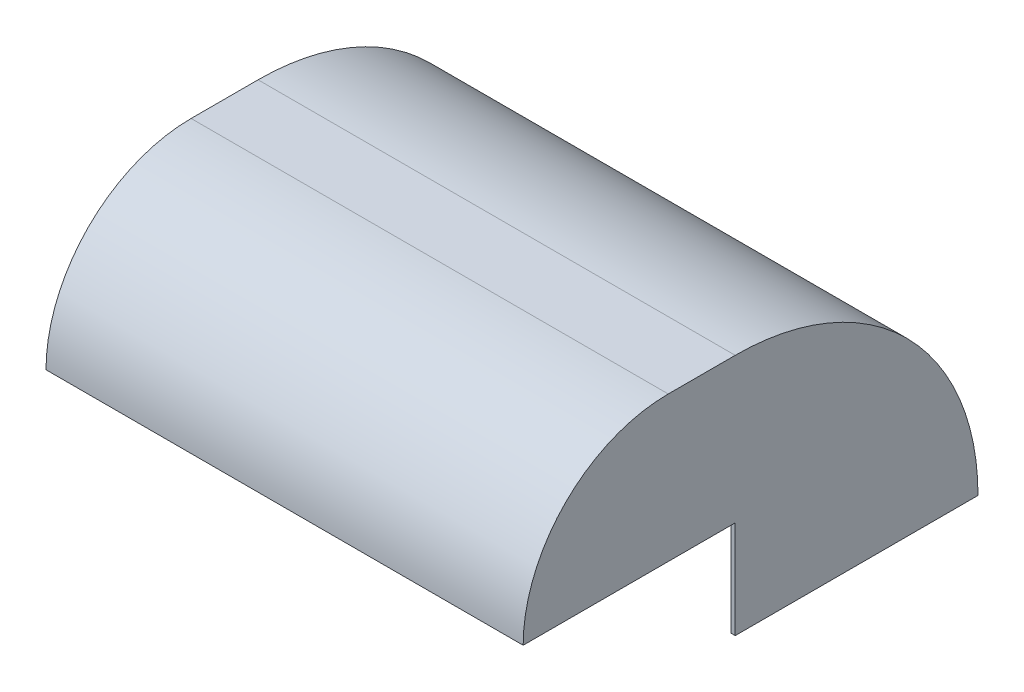
SolidWorks part; units mm, degrees
ref_plane "Front Plane" through (0, 0, 0) normal (0, 0, 1) x (1, 0, 0)
ref_plane "Top Plane" through (0, 0, 0) normal (0, 1, 0) x (1, 0, 0)
ref_plane "Right Plane" through (0, 0, 0) normal (1, 0, 0) x (0, 0, -1)
sketch "Sketch1" plane through (0, 0, 0) normal (0, 1, 0) x (1, 0, 0)
  line L0 (-16.4646, 32.3013) -> (-16.4646, -18.4987)
  line L1 (-13.2896, 29.1263) -> (13.6979, 29.1263)
  line L2 (-13.2896, 29.1263) -> (-13.2896, -15.3237)
  line L3 (-13.2896, -15.3237) -> (13.6979, -15.3237)
  line L4 (13.6979, 29.1263) -> (13.6979, -15.3237)
  line L5 (-16.4646, -18.4987) -> (16.8729, -18.4987)
  line L6 (16.8729, 32.3013) -> (16.8729, -18.4987)
  line L7 (-16.4646, 32.3013) -> (16.8729, 32.3013)
  line L8 (-16.4646, 32.3013) -> (-132.3521, 32.3013)
  line L9 (-132.3521, 32.3013) -> (-132.3521, -27.5039)
  line L10 (-248.2396, 32.3013) -> (-281.5771, 32.3013)
  line L11 (-281.5771, 32.3013) -> (-281.5771, -18.4987)
  line L12 (-248.2396, -18.4987) -> (-281.5771, -18.4987)
  line L13 (-248.2396, 32.3013) -> (-248.2396, -18.4987)
  line L14 (-251.4146, 29.1263) -> (-251.4146, -15.3237)
  line L15 (-251.4146, -15.3237) -> (-278.4021, -15.3237)
  line L16 (-278.4021, 29.1263) -> (-278.4021, -15.3237)
  line L17 (-251.4146, 29.1263) -> (-278.4021, 29.1263)
  line L18 (-13.2896, -15.3237) -> (-251.4146, -15.3237) construction
  dimension "D1" = 3.175
  dimension "D2" = 13.6979
  dimension "D3" = 13.2896
  dimension "D4" = 132.3521
  dimension "D5" = 29.1263
  dimension "D6" = 15.3237
  dimension "D7" = 27.5039
extrude "Boss-Extrude1" add sketch "Sketch1" along normal blind 25.4 contours L4 L1 L2 L3 | L0 L5 L6 L7 region at (0.2042, 0, -6.9013)
fillet "Fillet2" radius 2.54 4 edges at (13.6979, 12.7, 15.3237) (13.6979, 12.7, -29.1263) (-13.2896, 12.7, 15.3237) (-13.2896, 12.7, -29.1263)
sketch "Sketch2" plane through (0, 25.4, 0) normal (0, 1, 0) x (1, 0, 0)
  line L1 (16.8729, -18.4987) -> (-16.4646, -18.4987)
  line L2 (16.8729, -18.4987) -> (16.8729, 32.3013)
  line L3 (16.8729, 32.3013) -> (-16.4646, 32.3013)
  line L4 (-16.4646, -18.4987) -> (-16.4646, 32.3013)
extrude "Boss-Extrude2" add sketch "Sketch2" along normal blind 1.5875
extrude "Boss-Extrude3" add sketch "Sketch1<5>" along normal blind 26.9875 separate body contours L10 L11 L12 L13
sketch "Sketch1<5>" plane through (0, 0, 0) normal (0, 1, 0) x (1, 0, 0) same geometry as "Sketch1"
extrude "Cut-Extrude1" cut sketch "Sketch1<6>" along normal blind 25.4 contours L15 L16 L17 L14
sketch "Sketch1<6>" plane through (0, 0, 0) normal (0, 1, 0) x (1, 0, 0) same geometry as "Sketch1"
fillet "Fillet4" radius 2.54 4 edges at (-251.4146, 12.7, -29.1263) (-278.4021, 12.7, -29.1263) (-251.4146, 12.7, 15.3237) (-278.4021, 12.7, 15.3237)
ref_plane "Plane2" through (16.8729, 0, 0) normal (1, 0, 0) x (0, 0, -1)
sketch "Sketch3" plane through (16.8729, 0, 0) normal (1, 0, 0) x (0, 0, -1)
  line L0 (32.3013, 26.9875) -> (32.3013, -157.1625)
sketch "Sketch4" plane through (16.8729, 0, 0) normal (1, 0, 0) x (0, 0, -1)
  line L0 (32.3013, -157.1625) -> (216.4513, -157.1625)
  line L2 (32.3013, -157.1625) -> (32.3013, 26.9875)
  circle A0 centre (32.3013, -157.1625) radius 184.15
  circle A1 centre (32.3013, -157.1625) radius 180.975
sketch "Sketch5" plane through (0, 0, 0) normal (0, 1, 0) x (1, 0, 0)
  line L0 (16.8729, -18.4987) -> (-281.5771, -18.4987)
extrude "Boss-Extrude4" add sketch "Sketch4" against normal blind 330.2 and the other way blind 31.75 contours A1 L0 A0 L2 region at (16.8729, -27.3524, -162.1115)
ref_plane "Plane3" through (0, 0, -32.3013) normal (0, 0, 1) x (1, 0, 0)
sketch "Sketch6" plane through (0, 0, -32.3013) normal (0, 0, 1) x (1, 0, 0)
  line L1 (-248.2396, 26.9875) -> (-16.4646, 26.9875)
  line L2 (-248.2396, 26.9875) -> (-248.2396, 23.8125)
  line L3 (-248.2396, 23.8125) -> (-16.4646, 23.8125)
  line L4 (-16.4646, 26.9875) -> (-16.4646, 23.8125)
extrude "Boss-Extrude5" add sketch "Sketch6" along normal through all contours L2 L1 L4 L3
sketch "Sketch7" plane through (16.8729, 0, 0) normal (1, 0, 0) x (0, 0, -1)
  line L0 (-18.4987, 26.9875) -> (-18.4987, -83.0707)
  line L1 (-18.4987, -83.0707) -> (-128.5569, -83.0707)
  circle A0 centre (-18.4987, -83.0707) radius 110.0582
  circle A1 centre (-18.4987, -83.0707) radius 106.8324
extrude "Boss-Extrude6" add sketch "Sketch7" against normal blind 330.2 and the other way blind 31.75 contours A1 L0 A0 L1 region at (16.8729, 25.3746, 20.0551)
ref_plane "Plane4" through (48.6229, 0, 0) normal (1, 0, 0) x (0, 0, -1)
sketch "Sketch9" plane through (48.6229, 0, 0) normal (1, 0, 0) x (0, 0, -1)
  line L0 (32.3013, -157.1625) -> (32.3013, 26.9875)
  line L1 (32.3013, -157.1625) -> (216.4513, -157.1625)
  circle A0 centre (32.3013, -157.1625) radius 184.15
  circle A1 centre (32.3013, -157.1625) radius 180.975
extrude "Boss-Extrude7" add sketch "Sketch9" against normal blind 3.175 contours L1 A1 L0 region at (48.6229, -80.3543, -109.1095)
sketch "Sketch10" plane through (16.8729, 0, 0) normal (1, 0, 0) x (0, 0, -1)
  line L1 (32.3013, 26.9875) -> (-18.4987, 26.9875)
  line L2 (32.3013, 26.9875) -> (32.3013, 23.7617)
  line L3 (32.3013, 23.7617) -> (-18.4987, 23.7617)
  line L4 (-18.4987, 26.9875) -> (-18.4987, 23.7617)
extrude "Boss-Extrude8" add sketch "Sketch10" along normal blind 31.75
sketch "Sketch11" plane through (0, 0, -32.3013) normal (0, 0, 1) x (1, 0, 0)
  line L1 (45.4479, 23.7617) -> (48.6229, 23.7617)
  line L2 (45.4479, 23.7617) -> (45.4479, -157.1625)
  line L3 (45.4479, -157.1625) -> (48.6229, -157.1625)
  line L4 (48.6229, 23.7617) -> (48.6229, -157.1625)
extrude "Boss-Extrude9" add sketch "Sketch11" along normal blind 50.8
sketch "Sketch13" plane through (48.6229, 0, 0) normal (1, 0, 0) x (0, 0, -1)
  line L0 (-18.4987, -83.0707) -> (-128.5569, -83.0707)
  line L1 (-18.4987, -83.0707) -> (-18.4987, 26.9875)
  circle A0 centre (-18.4987, -83.0707) radius 110.0582
  circle A1 centre (-18.4987, -83.0707) radius 106.8324
extrude "Boss-Extrude12" add sketch "Sketch13" against normal blind 3.175 contours L1 A1 L0 region at (48.6229, -37.7296, 63.8398)
sketch "Sketch14" plane through (-281.5771, 0, 0) normal (-1, 0, 0) x (0, 0, 1)
  line L1 (-32.3013, 26.9875) -> (18.4987, 26.9875)
  line L2 (-32.3013, 26.9875) -> (-32.3013, 23.7617)
  line L3 (-32.3013, 23.7617) -> (18.4987, 23.7617)
  line L4 (18.4987, 26.9875) -> (18.4987, 23.7617)
extrude "Boss-Extrude13" add sketch "Sketch14" along normal blind 31.75
ref_plane "Plane5" through (-313.3271, 0, 0) normal (-1, 0, 0) x (0, 0, 1)
sketch "Sketch15" plane through (-313.3271, 0, 0) normal (-1, 0, 0) x (0, 0, 1)
  line L0 (-32.3013, -157.1625) -> (-32.3013, 26.9875)
  line L1 (-32.3013, -157.1625) -> (-216.4513, -157.1625)
  circle A0 centre (-32.3013, -157.1625) radius 184.15
  circle A1 centre (-32.3013, -157.1625) radius 180.975
extrude "Boss-Extrude14" add sketch "Sketch15" against normal blind 3.175 contours L0 A1 L1 region at (-313.3271, -80.3543, -109.1095)
sketch "Sketch17" plane through (0, 23.7617, 0) normal (0, -1, 0) x (1, 0, 0)
  line L1 (-310.1521, -32.3013) -> (-313.3271, -32.3013)
  line L2 (-310.1521, -32.3013) -> (-310.1521, 18.4987)
  line L3 (-310.1521, 18.4987) -> (-313.3271, 18.4987)
  line L4 (-313.3271, -32.3013) -> (-313.3271, 18.4987)
extrude "Boss-Extrude15" add sketch "Sketch17" along normal up to vertex (106.8324 mm away) contours L2 L1 L4 L3 up to point (45.4479, -83.0707, 18.4987)
sketch "Sketch18" plane through (-313.3271, 0, 0) normal (-1, 0, 0) x (0, 0, 1)
  line L0 (18.4987, -83.0707) -> (128.5569, -83.0707)
  line L1 (18.4987, -83.0707) -> (18.4987, 26.9875)
  circle A0 centre (18.4987, -83.0707) radius 110.0582
  circle A1 centre (18.4987, -83.0707) radius 106.8324
extrude "Boss-Extrude16" add sketch "Sketch18" against normal blind 3.175 contours L0 A1 L1 region at (-313.3271, -37.7296, 63.8398)
sketch "Sketch21" plane through (48.6229, 0, 0) normal (1, 0, 0) x (0, 0, -1)
  line L1 (32.3013, -157.1625) -> (-18.4987, -157.1625)
  line L2 (32.3013, -157.1625) -> (32.3013, -83.0707)
  line L3 (32.3013, -83.0707) -> (-18.4987, -83.0707)
  line L4 (-18.4987, -157.1625) -> (-18.4987, -83.0707)
extrude "Cut-Extrude2" cut sketch "Sketch21" against normal up to next
